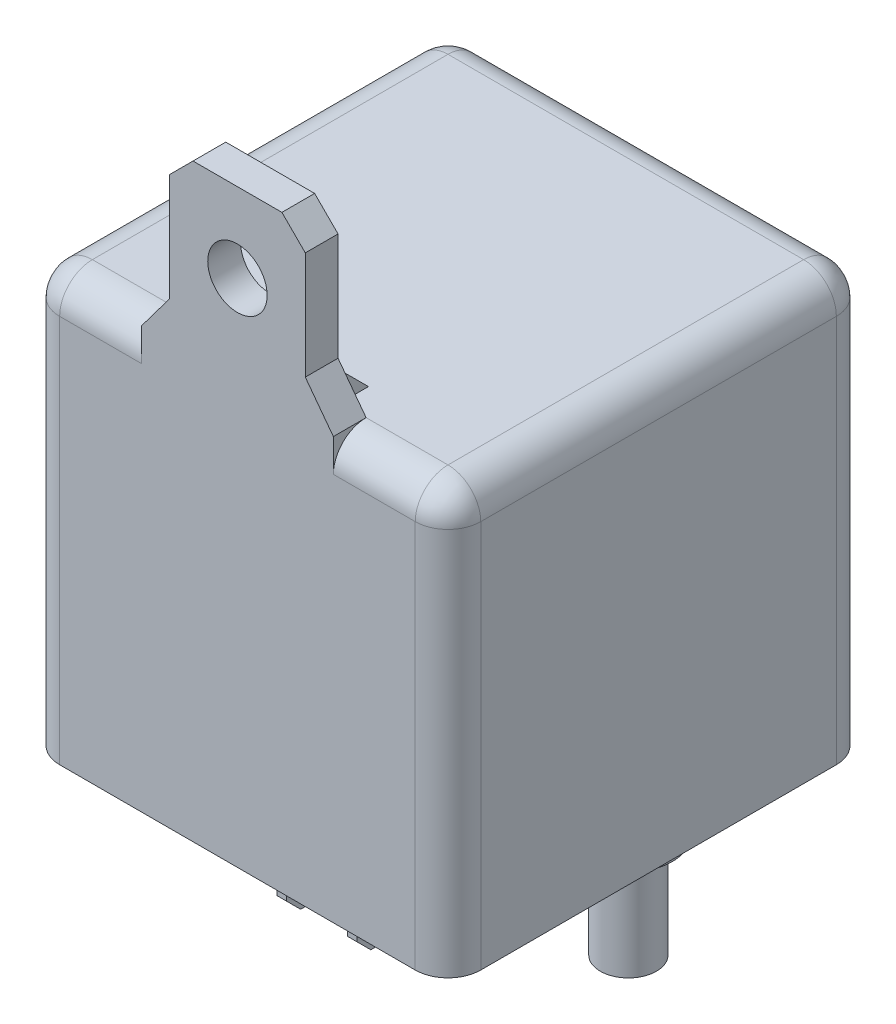
SolidWorks part; units mm, degrees
ref_plane "正面" through (0, 0, 0) normal (0, 0, 1) x (1, 0, 0)
ref_plane "平面" through (0, 0, 0) normal (0, 1, 0) x (1, 0, 0)
ref_plane "右側面" through (0, 0, 0) normal (1, 0, 0) x (0, 0, -1)
sketch "ｽｹｯﾁ1" plane through (0, 0, 0) normal (0, 1, 0) x (1, 0, 0)
  line L1 (-22.5, -22.5) -> (22.5, -22.5)
  line L2 (-22.5, -22.5) -> (-22.5, 22.5)
  line L3 (-22.5, 22.5) -> (22.5, 22.5)
  line L4 (22.5, -22.5) -> (22.5, 22.5)
  line L5 (-22.5, -22.5) -> (22.5, 22.5) construction
  line L6 (-22.5, 22.5) -> (22.5, -22.5) construction
  point P0 (0, 0)
  dimension "D1" = 45
extrude "ﾎﾞｽ - 押し出し1" add sketch "ｽｹｯﾁ1" along normal blind 45
fillet "ﾌｨﾚｯﾄ1" radius 3.5 8 edges at (0, 45, 22.5) (-22.5, 45, 0) (0, 45, -22.5) (22.5, 45, 0) (-22.5, 22.5, -22.5) (22.5, 22.5, -22.5) (22.5, 22.5, 22.5) (-22.5, 22.5, 22.5)
sketch "ｽｹｯﾁ2" plane through (0, 45, 0) normal (0, 1, 0) x (1, 0, 0)
  line L0 (19, -22.5) -> (-19, -22.5) construction
  line L1 (-7.25, -19) -> (7.25, -19)
  line L2 (-7.25, -19) -> (-7.25, -22.5)
  line L3 (-7.25, -22.5) -> (7.25, -22.5)
  line L4 (7.25, -19) -> (7.25, -22.5)
  point P6 (0, -19)
  dimension "D1" = 14.5
  dimension "D2" = 3.5
extrude "ﾎﾞｽ - 押し出し2" add sketch "ｽｹｯﾁ2" along normal blind 18 and the other way blind 5
sketch "ｽｹｯﾁ3" plane through (0, 0, 19) normal (0, 0, -1) x (-1, 0, 0)
  line L0 (7.25, 45) -> (-7.25, 45) construction
  line L5 (0, 63) -> (0, 45) construction
  line L6 (-7.25, 63) -> (7.25, 63) construction
sketch "ｽｹｯﾁ4" plane through (0, 0, 22.5) normal (0, 0, 1) x (1, 0, 0)
  line L0 (-7.25, 63) -> (-7.25, 41.5) construction
  line L1 (-19, 41.5) -> (-19, 0) construction
  line L2 (-19, 0) -> (19, 0) construction
  line L3 (19, 0) -> (19, 41.5) construction
  line L4 (7.25, 41.5) -> (7.25, 63) construction
  line L5 (7.25, 63) -> (-7.25, 63) construction
  line L6 (7.25, 41.5) -> (7.25, 45) construction
  line L7 (19, 41.5) -> (19, 45) construction
  line L8 (19, 45) -> (7.25, 45) construction
  line L9 (-7.25, 45) -> (-7.25, 41.5) construction
  line L10 (-7.25, 45) -> (-19, 45) construction
  line L11 (-19, 45) -> (-19, 41.5) construction
  line L12 (-7.25, 63) -> (-7.25, 41.5)
  line L13 (-19, 41.5) -> (-19, 0)
  line L14 (-19, 0) -> (19, 0)
  line L15 (19, 0) -> (19, 41.5)
  line L16 (7.25, 41.5) -> (7.25, 63)
  line L17 (7.25, 63) -> (-7.25, 63)
  line L18 (7.25, 41.5) -> (7.25, 45)
  line L19 (19, 41.5) -> (19, 45)
  line L20 (19, 45) -> (7.25, 45)
  line L21 (-7.25, 45) -> (-7.25, 41.5)
  line L22 (-7.25, 45) -> (-19, 45)
  line L23 (-19, 45) -> (-19, 41.5)
  line L24 (-10.25, 41.5) -> (-10.25, 45)
  line L25 (-7.25, 41.5) -> (-19, 41.5) construction
  line L26 (-10.25, 45) -> (-7.25, 49)
  line L27 (0, 63) -> (0, 0) construction
  line M5 (-7.25, 41.5) -> (-19, 41.5)
  dimension "D1" = 3
  dimension "D2" = 4
extrude "ﾎﾞｽ - 押し出し3" add sketch "ｽｹｯﾁ4" against normal blind 3.5 contours L26 L22 L12 | L24 L12 L22 M5 region at (-8.25, 46.3333, 22.5) region at (-8.75, 43.25, 22.5)
mirror "ﾐﾗｰ1" about plane through (0, 0, 0) normal (1, 0, 0) of "ﾎﾞｽ - 押し出し3"
chamfer "面取り1" distance 2.5 angle 45 2 edges at (7.25, 63, 20.75) (-7.25, 63, 20.75)
sketch "ｽｹｯﾁ5" plane through (0, 0, 19) normal (0, 0, -1) x (-1, 0, 0)
  line L0 (0, 63) -> (0, 45) construction
  line L1 (0, 63) -> (0, 45) construction
  line L2 (-4.75, 63) -> (4.75, 63) construction
  circle A0 centre (0, 54.525) radius 3.175
  dimension "D1" = 6.35
  dimension "D2" = 8.475
extrude "ｶｯﾄ - 押し出し1" cut sketch "ｽｹｯﾁ5" against normal blind 3.5
sketch "ｽｹｯﾁ6" plane through (0, 0, 19) normal (0, 0, -1) x (-1, 0, 0)
  line L0 (0, 63) -> (0, 45) construction
  line L1 (-7.5, 45) -> (-5.5, 45)
  line L2 (-7.5, 45) -> (-7.5, 48)
  line L3 (-7.5, 48) -> (-5.5, 48)
  line L4 (-5.5, 45) -> (-5.5, 48)
  line L5 (0, 63) -> (0, 45) construction
  line L8 (4.75, 63) -> (-4.75, 63)
  line L9 (-4.75, 63) -> (-7.25, 60.5)
  line L10 (-7.25, 60.5) -> (-7.25, 49)
  line L11 (-7.25, 49) -> (-10.25, 45)
  line L12 (-10.25, 45) -> (10.25, 45)
  line L13 (10.25, 45) -> (7.25, 49)
  line L14 (7.25, 49) -> (7.25, 60.5)
  line L15 (7.25, 60.5) -> (4.75, 63)
  line L16 (4.75, 63) -> (-4.75, 63)
  line L17 (-4.75, 63) -> (-7.25, 60.5)
  line L18 (-7.25, 60.5) -> (-7.25, 49)
  line L19 (-7.25, 49) -> (-10.25, 45)
  line L20 (-10.25, 45) -> (10.25, 45)
  line L21 (10.25, 45) -> (7.25, 49)
  line L22 (7.25, 49) -> (7.25, 60.5)
  line L23 (7.25, 60.5) -> (4.75, 63)
  line M18 (-10.25, 45) -> (10.25, 45)
  dimension "D2" = 5.5
  dimension "D3" = 2
  dimension "D4" = 3
  dimension "D1" = 0
extrude "ﾎﾞｽ - 押し出し4" add sketch "ｽｹｯﾁ6" along normal blind 3 contours L4 L3 L2 M18 region at (6.5, 46.5, 19)
chamfer "面取り2" distance 3 angle 45 1 edges at (6.5, 48, 16)
mirror "ﾐﾗｰ2" about plane through (0, 0, 0) normal (1, 0, 0) of "面取り2", "ﾎﾞｽ - 押し出し4"
sketch "ｽｹｯﾁ7" plane through (0, 0, 0) normal (0, -1, 0) x (1, 0, 0)
  line L0 (-21, 19) -> (-21, -19)
  line L1 (-19, -21) -> (19, -21)
  line L2 (21, -19) -> (21, 19)
  line L3 (19, 21) -> (-19, 21)
  line L4 (-22.5, 19) -> (-22.5, -19)
  line L5 (-19, -22.5) -> (19, -22.5)
  line L6 (22.5, -19) -> (22.5, 19)
  line L7 (19, 22.5) -> (-19, 22.5)
  line L8 (-22.5, 19) -> (-22.5, -19)
  line L9 (-19, -22.5) -> (19, -22.5)
  line L10 (22.5, -19) -> (22.5, 19)
  line L11 (19, 22.5) -> (-19, 22.5)
  line L12 (19, 20) -> (-19, 20)
  line L13 (-20, 19) -> (-20, -19)
  line L14 (-19, -20) -> (19, -20)
  line L15 (20, -19) -> (20, 19)
  arc A0 (-19, 21) -> (-21, 19) centre (-19, 19) ccw
  arc A1 (-21, -19) -> (-19, -21) centre (-19, -19) ccw
  arc A2 (19, -21) -> (21, -19) centre (19, -19) ccw
  arc A3 (21, 19) -> (19, 21) centre (19, 19) ccw
  arc A4 (-22.5, -19) -> (-19, -22.5) centre (-19, -19) ccw
  arc A5 (19, -22.5) -> (22.5, -19) centre (19, -19) ccw
  arc A6 (22.5, 19) -> (19, 22.5) centre (19, 19) ccw
  arc A7 (-19, 22.5) -> (-22.5, 19) centre (-19, 19) ccw
  arc A8 (-22.5, -19) -> (-19, -22.5) centre (-19, -19) ccw
  arc A9 (19, -22.5) -> (22.5, -19) centre (19, -19) ccw
  arc A10 (22.5, 19) -> (19, 22.5) centre (19, 19) ccw
  arc A11 (-19, 22.5) -> (-22.5, 19) centre (-19, 19) ccw
  arc A12 (-19, 20) -> (-20, 19) centre (-19, 19) ccw
  arc A13 (-20, -19) -> (-19, -20) centre (-19, -19) ccw
  arc A14 (19, -20) -> (20, -19) centre (19, -19) ccw
  arc A15 (20, 19) -> (19, 20) centre (19, 19) ccw
  dimension "D1" = 0
  dimension "D2" = 1.5
  dimension "D3" = 1
extrude "ｶｯﾄ - 押し出し2" cut sketch "ｽｹｯﾁ7" against normal blind 1.5 contours L2 A3 L3 A0 L0 A1 L1 A2 A15 L15 A14 L14 A13 L13 A12 L12 region at (-19.9942, 0, 19.9942)
chamfer "面取り3" distance 0.5 angle 45 8 edges at (0, 0, 21) (-20.4142, 0, 20.4142) (20.4142, 0, 20.4142) (-21, 0, 0) (21, 0, 0) (-20.4142, 0, -20.4142) (20.4142, 0, -20.4142) (0, 0, -21)
sketch "ｽｹｯﾁ8" plane through (0, 0, 0) normal (0, -1, 0) x (1, 0, 0)
  line L0 (0, 22.5) -> (0, -22.5) construction
  line L1 (-19, 22.5) -> (19, 22.5) construction
  line L2 (19, -22.5) -> (-19, -22.5) construction
  line L4 (3.25, 14) -> (4.25, 14)
  line L5 (3.25, 14) -> (3.25, 7.65)
  line L6 (3.25, 7.65) -> (4.25, 7.65)
  line L7 (4.25, 14) -> (4.25, 7.65)
  circle A0 centre (14.5, -4.775) radius 6
  point P12 (4.25, 10.825)
  dimension "D5" = 12
  dimension "D1" = 6.35
  dimension "D2" = 1
  dimension "D3" = 8.5
  dimension "D4" = 6.5
  dimension "D6" = 15.6
  dimension "D7" = 29
extrude "ﾎﾞｽ - 押し出し5" add sketch "ｽｹｯﾁ8" along normal blind 10.5 contours L7 L4 L5 L6 region at (3.75, 0, 10.825)
sketch "ｽｹｯﾁ9" plane through (0, 0, 0) normal (0, -1, 0) x (1, 0, 0)
  line L4 (4.25, 14) -> (3.25, 14)
  line L5 (4.25, 7.65) -> (4.25, 14)
  line L6 (3.25, 7.65) -> (4.25, 7.65)
  line L7 (3.25, 14) -> (3.25, 7.65)
  line L8 (4.25, 14) -> (3.25, 14)
  line L9 (4.25, 7.65) -> (4.25, 14)
  line L10 (3.25, 7.65) -> (4.25, 7.65)
  line L11 (3.25, 14) -> (3.25, 7.65)
  circle A1 centre (14.5, -4.775) radius 6
  circle A2 centre (14.5, -4.775) radius 6
  line M10 (20, -19) -> (20, 19)
  dimension "D1" = 0
  dimension "D2" = 0
extrude "ﾎﾞｽ - 押し出し6" add sketch "ｽｹｯﾁ9" along normal blind 1.5 and the other way blind 2 contours A2 M10 | A2 M10 region at (20.2007, 0, -4.775) region at (14.4175, 0, -4.775)
sketch "ｽｹｯﾁ10" plane through (0, -1.5, 0) normal (0, -1, 0) x (1, 0, 0)
  circle A0 centre (14.5, -4.775) radius 4.7
  dimension "D1" = 9.4
extrude "ﾎﾞｽ - 押し出し7" add sketch "ｽｹｯﾁ10" along normal blind 2
sketch "ｽｹｯﾁ11" plane through (0, -3.5, 0) normal (0, -1, 0) x (1, 0, 0)
  circle A0 centre (14.5, -4.775) radius 3
  dimension "D1" = 6
extrude "ﾎﾞｽ - 押し出し8" add sketch "ｽｹｯﾁ11" along normal blind 11
mirror "ﾐﾗｰ3" about plane through (0, 0, 0) normal (1, 0, 0) of "ﾎﾞｽ - 押し出し8", "ﾎﾞｽ - 押し出し7", "ﾎﾞｽ - 押し出し6", "ﾎﾞｽ - 押し出し5"
chamfer "面取り4" distance 1.5 angle 45 4 edges at (3.75, -10.5, 7.65) (-3.75, -10.5, 7.65) (-3.75, -10.5, 14) (3.75, -10.5, 14)
